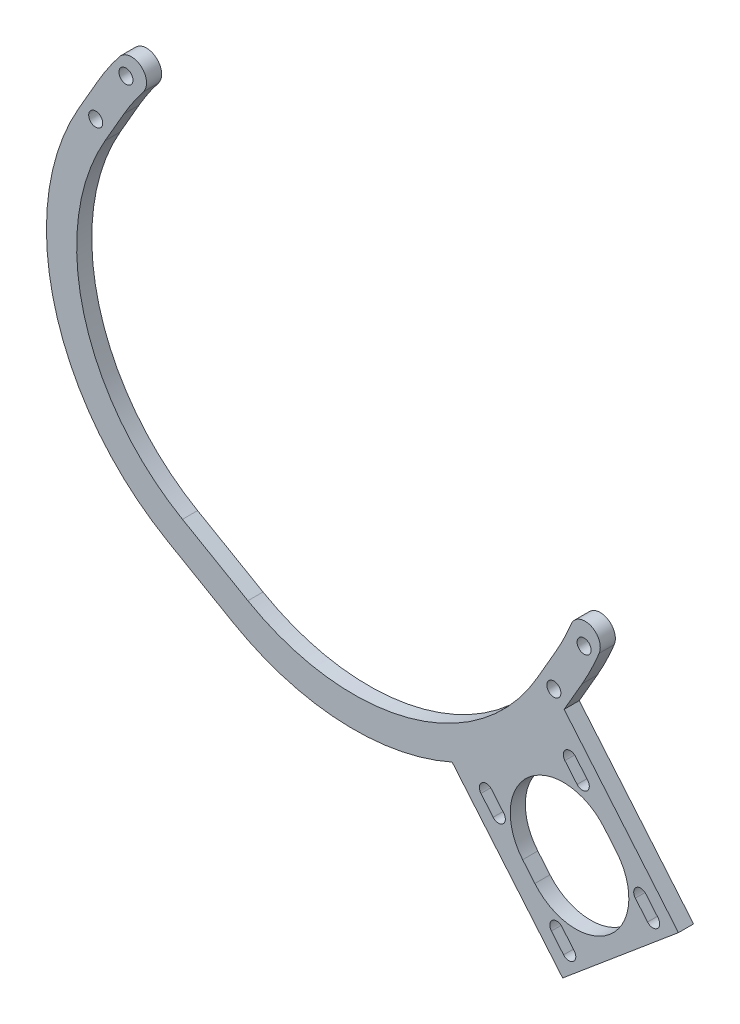
SolidWorks part; units mm, degrees
ref_plane "Front Plane" through (0, 0, 0) normal (0, 0, 1) x (1, 0, 0)
ref_plane "Top Plane" through (0, 0, 0) normal (0, 1, 0) x (1, 0, 0)
ref_plane "Right Plane" through (0, 0, 0) normal (1, 0, 0) x (0, 0, -1)
sketch "Sketch1" plane through (0, 0, -14.157) normal (0, 0, -1) x (-1, 0, 0)
  line L0 (-49.1723, -34.5021) -> (-53.1411, -27.628)
  line L1 (-2.2729, 1.7407) -> (29.3872, -53.0962) construction
  line L2 (20.2218, -53.0962) -> (27.0959, -49.1274)
  line L3 (33.9699, -45.1587) -> (20.2218, -53.0962) construction
  line L4 (17.0468, -47.5969) -> (23.9209, -43.6282)
  line L5 (-43.6731, -31.3271) -> (-47.6418, -24.453)
  line L6 (47.0648, 21.0604) -> (43.096, 27.9345)
  line L7 (30.7949, -39.6594) -> (23.9209, -43.6282)
  line L8 (33.9699, -45.1587) -> (27.0959, -49.1274)
  line L9 (52.564, 24.2354) -> (48.5953, 31.1095)
  arc A0 (-53.1411, -27.628) -> (-56.7299, -20.2712) centre (-2.2729, 1.7407) cw
  arc A3 (-61.0104, 1.7407) -> (-53.1411, -27.628) centre (-2.2729, 1.7407) ccw construction
  circle A4 centre (-53.5664, -20.5413) radius 1.1303 construction
  arc A5 (-49.1723, -34.5021) -> (20.2218, -53.0962) centre (-5.1782, -9.1021) ccw
  arc A6 (-43.6731, -31.3271) -> (17.0468, -47.5969) centre (-5.1782, -9.1021) ccw
  arc A7 (-47.6418, -24.453) -> (-50.8427, -17.8916) centre (-2.2729, 1.7407) cw
  arc A8 (-56.7299, -20.2712) -> (-50.8427, -17.8916) centre (-53.7863, -19.0814) cw
  arc A9 (44.0185, 37.8959) -> (39.014, 33.9872) centre (41.5163, 35.9416) ccw
  arc A10 (43.096, 27.9345) -> (39.014, 33.9872) centre (-2.2729, 1.7407) ccw
  arc A11 (47.0648, 21.0604) -> (30.7949, -39.6594) centre (8.5699, -1.1646) cw
  arc A12 (52.564, 24.2354) -> (33.9699, -45.1587) centre (8.5699, -1.1646) cw
  arc A13 (48.5953, 31.1095) -> (44.0185, 37.8959) centre (-2.2729, 1.7407) ccw
  dimension "D1" = 3.175
  dimension "D2" = 6.35
extrude "Boss-Extrude1" add sketch "Sketch1" along normal blind 3.175
ref_plane "Plane1" through (0, -58.42, 0) normal (0, 1, 0) x (-1, 0, 0)
ref_plane "Plane2" through (0, 0, -14.157) normal (0, 0, 1) x (1, 0, 0)
ref_axis "Axis2" through (-66.4483, 0, -14.157) along (1, 0, 0)
ref_axis "Axis3" through (0, 0, -25.4783) along (0, 0, 1)
ref_point "Point1"
ref_axis "Axis4" through (0, -70.9509, -14.157) along (0, 1, 0)
sketch "Sketch6" plane through (0, 0, -14.157) normal (0, 0, 1) x (1, 0, 0)
  line L0 (0, 0) -> (48.2094, -57.4538) construction
  line L1 (0, -70.9509) -> (0, 0.8498) construction
  line L10 (73.3865, -62.7615) -> (49.0646, -83.17)
  line L15 (73.3865, -62.7615) -> (47.3543, -31.7375)
  line L16 (49.0646, -83.17) -> (23.0324, -52.146)
  line L17 (47.3543, -31.7375) -> (23.0324, -52.146)
  line L18 (73.3865, -62.7615) -> (23.0324, -52.146) construction
  line L19 (49.0646, -83.17) -> (47.3543, -31.7375) construction
  line L20 (49.2253, -58.6644) -> (51.7886, -61.7193) construction
  line L21 (57.7866, -51.4807) -> (60.3499, -54.5355)
  line L22 (40.664, -65.8482) -> (43.2273, -68.9031)
  line L23 (31.8996, -55.917) -> (53.9198, -82.1596) construction
  line L24 (50.3704, -77.9296) -> (47.8071, -74.8748) construction
  line L25 (71.1509, -66.8939) -> (48.7841, -40.2382) construction
  line L26 (49.2613, -78.8602) -> (46.698, -75.8054)
  line L27 (51.4795, -76.999) -> (48.9162, -73.9441)
  line L28 (33.015, -57.2462) -> (35.5783, -60.3011) construction
  line L29 (34.1241, -56.3156) -> (36.6874, -59.3704)
  line L30 (31.9059, -58.1769) -> (34.4692, -61.2317)
  line L31 (50.6435, -42.4541) -> (53.2068, -45.509) construction
  line L32 (51.7526, -41.5235) -> (54.3159, -44.5784)
  line L33 (49.5345, -43.3848) -> (52.0978, -46.4396)
  line L34 (65.4356, -60.0827) -> (67.9989, -63.1375) construction
  line L35 (66.5447, -59.152) -> (69.108, -62.2069)
  line L36 (64.3265, -61.0133) -> (66.8899, -64.0681)
  line L37 (35.5783, -60.3011) -> (53.2068, -45.509) construction
  arc A0 (49.2613, -78.8602) -> (51.4795, -76.999) centre (50.3704, -77.9296) ccw
  arc A1 (48.9162, -73.9441) -> (46.698, -75.8054) centre (47.8071, -74.8748) ccw
  arc A2 (-17.0468, -47.5969) -> (43.6731, -31.3271) centre (5.1782, -9.1021) ccw construction
  arc A3 (57.7866, -51.4807) -> (40.664, -65.8482) centre (49.2253, -58.6644) ccw
  arc A4 (43.2273, -68.9031) -> (60.3499, -54.5355) centre (51.7886, -61.7193) ccw
  arc A5 (34.1241, -56.3156) -> (31.9059, -58.1769) centre (33.015, -57.2462) ccw
  arc A6 (34.4692, -61.2317) -> (36.6874, -59.3704) centre (35.5783, -60.3011) ccw
  arc A7 (51.7526, -41.5235) -> (49.5345, -43.3848) centre (50.6435, -42.4541) ccw
  arc A8 (52.0978, -46.4396) -> (54.3159, -44.5784) centre (53.2068, -45.509) ccw
  arc A9 (66.5447, -59.152) -> (64.3265, -61.0133) centre (65.4356, -60.0827) ccw
  arc A10 (66.8899, -64.0681) -> (69.108, -62.2069) centre (67.9989, -63.1375) ccw
  point P3 (50.507, -60.1919)
  point P25 (49.0888, -76.4022)
  point P30 (34.2967, -58.7736)
  point P37 (51.9252, -43.9816)
  point P44 (66.7173, -61.6101)
  dimension "D4" = 11.176
  dimension "D5" = 11.5062
  dimension "D8" = 1.4478
  dimension "D9" = 23.0124
  dimension "D14" = 1.4478
  dimension "D15" = 1.4478
  dimension "D16" = 1.4478
  dimension "D19" = 3.9878
  dimension "D1" = 40
  dimension "D2" = 95.25
  dimension "D3" = 31.75
  dimension "D6" = 11.5062
  dimension "D7" = 3.9878
  dimension "D10" = 23.0124
  dimension "D11" = 3.9878
  dimension "D12" = 3.9878
  dimension "D13" = 3.9878
  dimension "D17" = 3.175
  dimension "D18" = 3.175
  dimension "D20" = 11.5062
extrude "Boss-Extrude2" add sketch "Sketch6" against normal up to surface (3.175 mm away) up to face at (-5.7343, -12.1282, -17.332)
hole_wizard "#4 Clearance Hole1" positions "Sketch5" profile "Sketch4" hole size "#4" standard "Ansi Inch" end condition through all
sketch "Sketch5" plane through (0, 0, -17.332) normal (0, 0, -1) x (-1, 0, 0)
  circle A1 centre (-53.5664, -20.5413) radius 1.1303 construction
  circle A2 centre (49.0206, 24.0227) radius 1.1303 construction
  point P0 (-53.5664, -20.5413)
  point P5 (-47.2164, -31.5398)
  point P8 (42.6706, 35.0212)
  point P11 (49.0206, 24.0227)
sketch "Sketch4" plane through (53.5664, -20.5413, -17.332) normal (1, 0, 0) x (0, 1, 0)
  line L0 (0, 0) -> (0, 3.175)
  line L1 (0, 3.175) -> (1.4732, 3.175)
  line L2 (1.4732, 3.175) -> (1.4732, 0)
  line L5 (1.4732, 0) -> (0, 0)
  line L11 (0, -6.35) -> (0, 107.95) construction
  dimension "Thru Hole Dia." = 2.9464
  dimension "Thru Hole Depth" = 3.175
